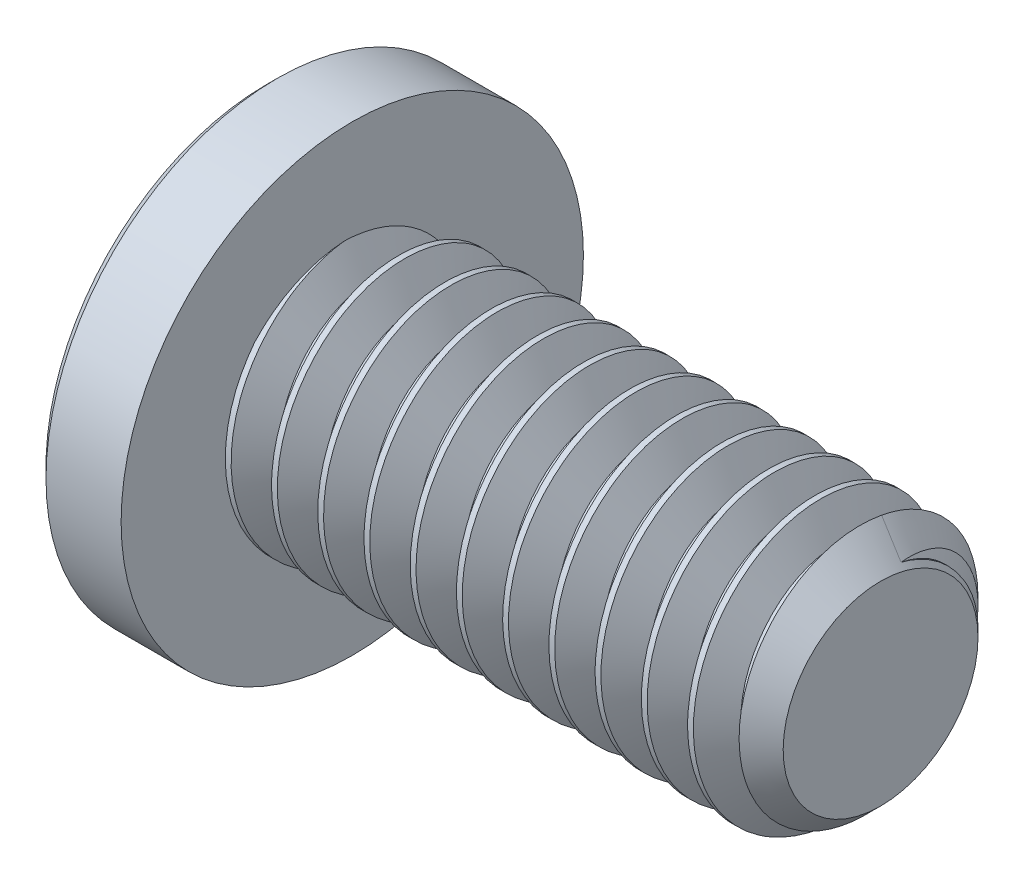
SolidWorks part; units mm, degrees
ref_plane "Front Plane" through (0, 0, 0) normal (0, 0, 1) x (1, 0, 0)
ref_plane "Top Plane" through (0, 0, 0) normal (0, 1, 0) x (1, 0, 0)
ref_plane "Right Plane" through (0, 0, 0) normal (1, 0, 0) x (0, 0, -1)
sketch "Sketch1" plane through (0, 0, 0) normal (0, 0, 1) x (1, 0, 0)
  line L0 (4, 0) -> (-4, 0) construction
  line L1 (4, 2) -> (4, -2) construction
  line L2 (-4, 3.5) -> (-4, -3.5) construction
  line L3 (-4, 3.5) -> (-5.1375, 3.5) construction
  line L4 (-5.1375, 3.5) -> (-5.3, 3.3375) construction
  line L5 (-5.3, 3.3375) -> (-5.3, -3.3375) construction
  line L6 (-5.3, -3.3375) -> (-5.1375, -3.5) construction
  line L7 (-5.1375, -3.5) -> (-4, -3.5) construction
  point P7 (-2.88, 0)
  point P12 (1.2, -2)
  dimension "D1" = 45
  dimension "Dec." = 4
  dimension "Length" = 8
  dimension "Head Dia" = 7
  dimension "Head Height" = 1.3
  dimension "Hex Depth" = 2.42
  dimension "Chamfer" = 0.1625
  dimension "D2" = 2.8
ref_plane "Plane1" through (4, 0, 0) normal (1, 0, 0) x (0, 0, -1)
ref_plane "Plane2" through (-5.3, 0, 0) normal (1, 0, 0) x (0, 0, -1)
sketch "Sketch2" plane through (4, 0, 0) normal (1, 0, 0) x (0, 0, -1)
  circle A0 centre (0, 0) radius 2
extrude "Boss-Extrude1" add sketch "Sketch2" against normal up to vertex (8 mm away) up to point (-4, 0, 0)
sketch "Sketch3" plane through (4, 0, 0) normal (1, 0, 0) x (0, 0, -1)
  circle A0 centre (0, 0) radius 2 construction
  circle A1 centre (0, 0) radius 2
curve "Helix/Spiral1" pitch 0.7 height 8.7 radius 2 centre (4, 0, 0) axis (-1, 0, 0) start towards (0, 1, 0) parameters "Pitch"=0.7
chamfer "Chamfer1" distance 0.525 angle 45 1 edges at (4, 0, -2)
sketch "Sketch5" plane through (0, 0, 0) normal (0, 0, 1) x (1, 0, 0)
  line L0 (3.6937, 2) -> (4.3062, 2)
  line L1 (4.3062, 2) -> (4.0437, 1.5453)
  line L2 (4.0437, 1.5453) -> (3.9562, 1.5453)
  line L3 (3.9562, 1.5453) -> (3.6937, 2)
  line L4 (4, 1.5453) -> (4, 2) construction
  line L5 (3.825, 1.7727) -> (4.175, 1.7727) construction
  dimension "D1" = 60
  dimension "D2" = 0.35
  dimension "D3" = 0.0875
sweep "Cut-Sweep1" cut profiles "Sketch5" path "Helix/Spiral1" align with end faces yes
sketch "Sketch4" plane through (-5.3, 0, 0) normal (1, 0, 0) x (0, 0, -1)
  line L0 (-3.5, 0.7937) -> (3.5, 0.7937) construction
  line L1 (0, 1.4434) -> (-1.25, 0.7217)
  line L2 (-1.25, 0.7217) -> (-1.25, -0.7217)
  line L3 (-1.25, -0.7217) -> (0, -1.4434)
  line L4 (0, -1.4434) -> (1.25, -0.7217)
  line L5 (1.25, -0.7217) -> (1.25, 0.7217)
  line L6 (1.25, 0.7217) -> (0, 1.4434)
  line L7 (0, 0) -> (0, 0.7937) construction
  circle A0 centre (0, 0) radius 1.25 construction
  dimension "Hex Size" = 2.5
  dimension "D1" = 7
  dimension "D2" = 0.7937
sketch "Sketch6" plane through (0, 0, 0) normal (0, 0, 1) x (1, 0, 0)
  line L0 (-5.1375, 3.5) -> (-5.3, 3.3375) construction
  line L1 (-4, 3.5) -> (-5.1375, 3.5) construction
  line L2 (-4, 3.5) -> (-4, -3.5) construction
  line L3 (-5.3, 3.3375) -> (-5.3, -3.3375) construction
  line L4 (-5.1375, 3.5) -> (-5.3, 3.3375)
  line L5 (-4, 3.5) -> (-5.1375, 3.5)
  line L6 (-4, 3.5) -> (-4, 0)
  line L7 (-5.3, 3.3375) -> (-5.3, 0)
  line L8 (-4, 0) -> (-5.3, 0) construction
  line L9 (-4, 0) -> (-5.3, 0)
revolve "Revolve1" add sketch "Sketch6" angle 360 about L8
extrude "Cut-Extrude1" cut sketch "Sketch4" along normal up to vertex (2.42 mm away) up to point (-2.88, 0, 0)
sketch "Sketch8" plane through (-5.3, 0, 0) normal (-1, 0, 0) x (0, 0, 1)
  circle A1 centre (0, 0) radius 1.4434
extrude "Cut-Extrude2" cut sketch "Sketch8" against normal through all draft 45
equation "\"D3@Helix/Spiral1\" = \"Length@Sketch1\"+\"Pitch@Helix/Spiral1\""
equation "\"D3@Sketch5\" = \"Pitch@Helix/Spiral1\"*.125"
equation "\"D2@Sketch5\" = \"Pitch@Helix/Spiral1\"*.50"
equation "\"D1@Chamfer1\" = \"Pitch@Helix/Spiral1\"*.75"
equation "\"D2@Sketch1\" = \"Pitch@Helix/Spiral1\"*4"
equation "\"D1@Sketch4\" = \"Head Dia@Sketch1\""
equation "\"Chamfer@Sketch1\" = \"Head Height@Sketch1\"/8"
